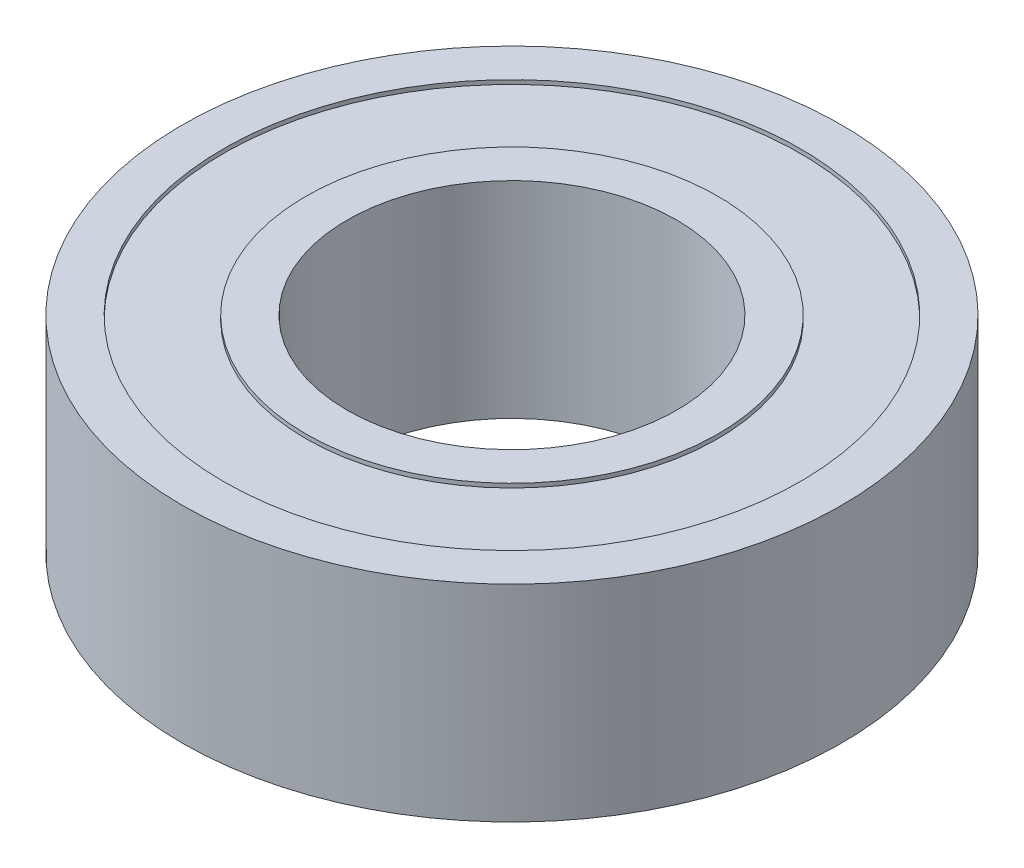
SolidWorks part; units mm, degrees
ref_plane "Front plane" through (0, 0, 0) normal (0, 0, 1) x (1, 0, 0)
ref_plane "Top plane" through (0, 0, 0) normal (0, 1, 0) x (1, 0, 0)
ref_plane "Right plane" through (0, 0, 0) normal (1, 0, 0) x (0, 0, -1)
ref_axis "Axis X" through (0, 0, 0) along (1, 0, 0)
ref_axis "Axis Y" through (0, 0, 0) along (0, 1, 0)
ref_axis "Axis Z" through (0, 0, 0) along (0, 0, 1)
sketch "Sketch1" plane through (0, 0, 0) normal (0, 1, 0) x (1, 0, 0)
  circle A0 centre (0, 0) radius 8
  circle A1 centre (0, 0) radius 4
  dimension "D1" = 16
  dimension "D2" = 8
extrude "Extrude1" add sketch "Sketch1" along normal blind 5
sketch "Sketch2" plane through (0, 5, 0) normal (0, 1, 0) x (1, 0, 0)
  circle A2 centre (0, 0) radius 7
  circle A3 centre (0, 0) radius 7
  circle A5 centre (0, 0) radius 5
  circle A6 centre (0, 0) radius 5
extrude "Extrude2" cut sketch "Sketch2" against normal blind 0.1
sketch "Sketch3" plane through (0, 0, 0) normal (0, -1, 0) x (1, 0, 0)
  circle A2 centre (0, 0) radius 7
  circle A3 centre (0, 0) radius 7
  circle A5 centre (0, 0) radius 5
  circle A6 centre (0, 0) radius 5
extrude "Extrude3" cut sketch "Sketch3" against normal blind 0.1
equation "\"motor_D\"= 49'Motor diameter"
equation "\"motor_H\"= 19'Motor heigh"
equation "\"motor_d1\"= 38.5'Seating diameter of screws on the fixed part of the motor"
equation "\"motor_s1\"= 2.5'Screws diameter on the fixed part of motor"
equation "\"motor_a2\"= 0'Seating parameter in rectangle of screws on the moving part of the motor"
equation "\"motor_s2\"= 3'Screws diameter on the moving part of motor"
equation "\"motor_Dc\"= 5'Central hole diameter of motor"
equation "\"bearing_d1\"= 8'Bearing inner diameter"
equation "\"bearing_d2\"= 16'Bearing external diameter"
equation "\"bearing h\"= 5'Bearing heigh"
equation "\"pin_d\"= 2'Pin diameter"
equation "\"pin_h\"= 13'Pin heigh"
equation "\"magnet_d1\"= 5'Magnet inner diameter"
equation "\"magnet_d2\"= 9.5'Magnet external diameter"
equation "\"magnet_h\"= 3'Magnet heigh"
equation "\"motor_b2\"= 0'Seating parameter in rectangle of screws on the moving part of the motor"
equation "\"motor_d2\"= 25'Seating diameter of screws on the moving part of the motor (if this parameter is not determine, write 0)"
equation "\"motor_cmd\"= 17'Central magnet mount diameter"
equation "\"motor_cmh\"= 1'Central magnet mount heigh (if not write 0)"
equation "\"motor_whR\"= 17'Distance from center of motor to wires"
equation "\"D1@Sketch1\"=\"bearing_d2\""
equation "\"D2@Sketch1\"=\"bearing_d1\""
equation "\"D1@Extrude1\"=\"bearing h\""
equation "\"D1@Sketch2\"=(\"bearing_d2\"-\"bearing_d1\")/2/4"
equation "\"D2@Sketch2\"=\"D1@Sketch2\""
equation "\"D1@Extrude2\"=0.1"
equation "\"D2@Sketch3\"=(\"bearing_d2\"-\"bearing_d1\")/2/4"
equation "\"D1@Sketch3\"=\"D2@Sketch3\""
equation "\"print_offset\"= 0.2'Offset for printing holes"
equation "\"ft_sensor_d1\"= 9.8"
equation "\"ft_sensor_d2\"= 24.9"
equation "\"ft_sensor_d3\"= 22.6'Inner diameter of "
equation "\"ft_sensor_h\"= 7.1"
equation "\"ft_sensor_whD\" = 5"
